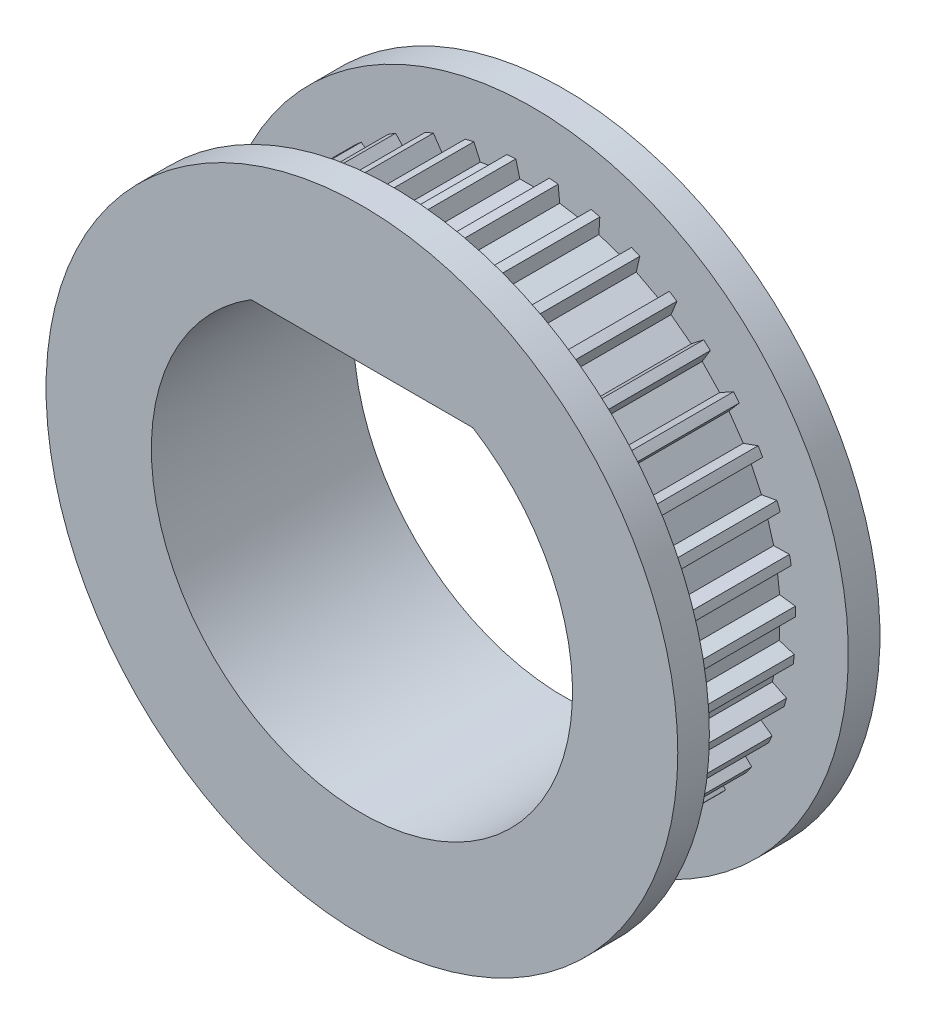
SolidWorks part; units mm, degrees
ref_plane "Front Plane" through (0, 0, 0) normal (0, 0, 1) x (1, 0, 0)
ref_plane "Top Plane" through (0, 0, 0) normal (0, 1, 0) x (1, 0, 0)
ref_plane "Right Plane" through (0, 0, 0) normal (1, 0, 0) x (0, 0, -1)
sketch "Sketch1" plane through (0, 0, 0) normal (0, 0, 1) x (1, 0, 0)
  circle A0 centre (0, 0) radius 12.5
  dimension "D1" = 25
extrude "Boss-Extrude1" add sketch "Sketch1" along normal mid plane 6.6
sketch "Sketch3" plane through (0, 0, 3.3) normal (0, 0, 1) x (1, 0, 0)
  circle A0 centre (0, 0) radius 15
  dimension "D1" = 30
sketch "Sketch2" plane through (0, 0, -3.3) normal (0, 0, -1) x (-1, 0, 0)
  circle A0 centre (0, 0) radius 15
  dimension "D1" = 30
sketch "Sketch4" plane through (0, 0, 3.3) normal (0, 0, 1) x (1, 0, 0)
  line L0 (-0.6, 11.75) -> (0.6, 11.75)
  line L1 (0.6, 11.75) -> (0.8, 12.5)
  line L2 (0.8, 12.5) -> (-0.8, 12.5)
  line L3 (-0.8, 12.5) -> (-0.6, 11.75)
  circle A0 centre (0, 0) radius 12.5 construction
  point P4 (-1.967, 18.9038)
  point P5 (-2.8978, 18.7672)
  point P6 (-1.3713, 18.4756)
  point P7 (-1.4024, 17.6875)
  point P10 (0, 11.75)
  dimension "D1" = 1.2
  dimension "D2" = 1.6
  dimension "D3" = 0.75
extrude "Cut-Extrude1" cut sketch "Sketch4" against normal up to surface (6.6 mm away) and the other way through all up to face at (12.5, 0, -3.3)
pattern_circular "CirPattern2" count 39 over 360 about axis through (0, 0, 3.3) along (0, 0, 1) of "Cut-Extrude1"
extrude "Boss-Extrude3" add sketch "Sketch2" along normal blind 1.5
extrude "Boss-Extrude4" add sketch "Sketch3" along normal blind 1.5 contours A0
sketch "Sketch6" plane through (0, 0, 4.8) normal (0, 0, 1) x (1, 0, 0)
  line L0 (-5.2678, 8.5) -> (5.2678, 8.5)
  circle A0 centre (0, 0) radius 10
  dimension "D1" = 20
  dimension "D2" = 8.5
extrude "Cut-Extrude3" cut sketch "Sketch6" against normal through all both and the other way through all contours L0 A0 region at (0, -0.3212, 4.8)
